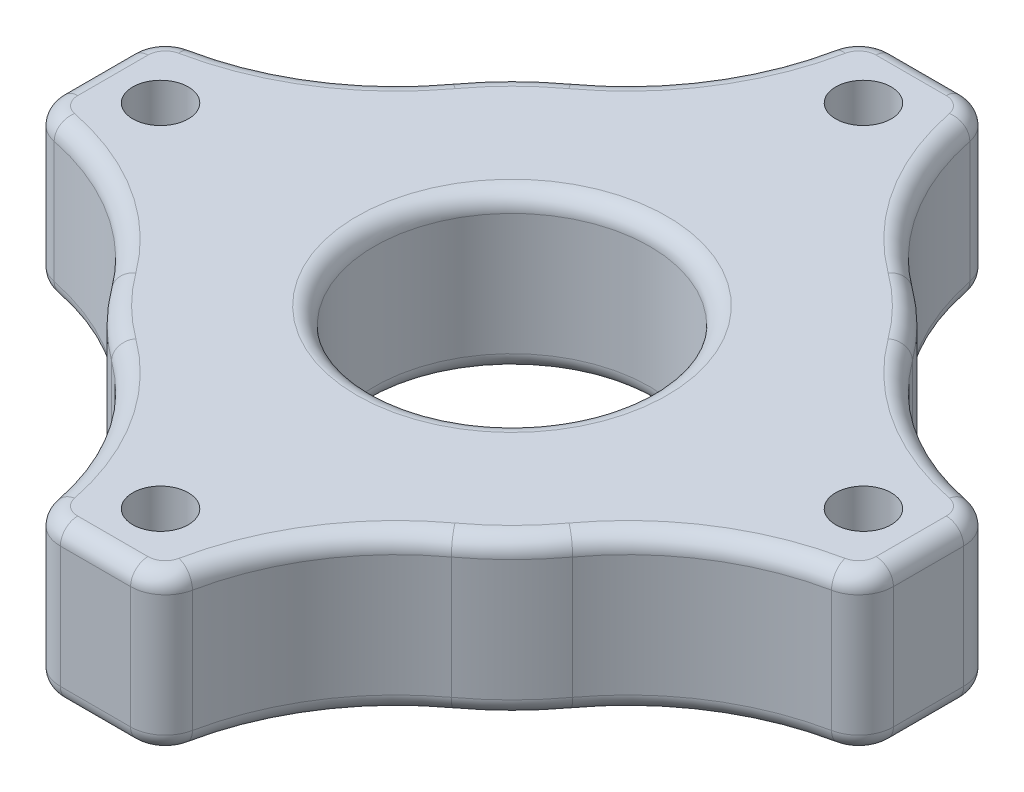
SolidWorks part; units mm, degrees
ref_plane "Front Plane" through (0, 0, 0) normal (0, 0, 1) x (1, 0, 0)
ref_plane "Top Plane" through (0, 0, 0) normal (0, 1, 0) x (1, 0, 0)
ref_plane "Right Plane" through (0, 0, 0) normal (1, 0, 0) x (0, 0, -1)
sketch "Geometry" plane through (0, 0, 0) normal (0, 1, 0) x (1, 0, 0)
  line L2 (-55, 0) -> (55, 0) construction
  line L3 (-24, -3.75) -> (24, -3.75) construction
  line L4 (-24, -3.75) -> (-24, 3.75) construction
  line L5 (-24, 3.75) -> (24, 3.75) construction
  line L6 (24, -3.75) -> (24, 3.75) construction
  line L7 (-24, -3.75) -> (24, 3.75) construction
  line L8 (-24, 3.75) -> (24, -3.75) construction
  line L9 (-3.75, -24) -> (3.75, -24) construction
  line L10 (-3.75, -24) -> (-3.75, 24) construction
  line L11 (-3.75, 24) -> (3.75, 24) construction
  line L12 (3.75, -24) -> (3.75, 24) construction
  line L13 (-3.75, -24) -> (3.75, 24) construction
  line L14 (-3.75, 24) -> (3.75, -24) construction
  line L15 (-16.0682, 3.75) -> (-24, 3.75)
  line L16 (-24, 3.75) -> (-24, -3.75)
  line L17 (-24, -3.75) -> (-16.0682, -3.75)
  line L18 (3.75, 16.0682) -> (3.75, 24)
  line L19 (3.75, 24) -> (-3.75, 24)
  line L20 (-3.75, 24) -> (-3.75, 16.0682)
  line L21 (16.0682, -3.75) -> (24, -3.75)
  line L22 (24, -3.75) -> (24, 3.75)
  line L23 (24, 3.75) -> (16.0682, 3.75)
  line L24 (-3.75, -16.0682) -> (-3.75, -24)
  line L25 (-3.75, -24) -> (3.75, -24)
  line L26 (3.75, -24) -> (3.75, -16.0682)
  circle A0 centre (0, 0) radius 7.9375
  circle A1 centre (0, 0) radius 16.5
  circle A2 centre (-20.25, 0) radius 1.6
  circle A3 centre (0, 20.25) radius 1.6
  circle A4 centre (20.25, 0) radius 1.6
  circle A5 centre (0, -20.25) radius 1.6
  circle A6 centre (-20.25, 0) radius 2.75
  circle A7 centre (0, 20.25) radius 2.75
  circle A8 centre (20.25, 0) radius 2.75
  circle A9 centre (0, -20.25) radius 2.75
  dimension "D1" = 15.875
  dimension "D2" = 33
  dimension "D6" = 3.2
  dimension "D8" = 5.5
  dimension "D3" = 7.5
  dimension "D4" = 24
  dimension "D5" = 3.75
  dimension "D7" = 4
  dimension "D9" = 4
  dimension "D10" = 4
extrude "Cap and Holes" add sketch "Geometry" along normal blind 9 contours A1 A0 | A1 L15 L16 L17 A6 | A1 L24 L25 L26 A9 | A1 L21 L22 L23 A8 | A1 L18 L19 L20 A7 | A7 A3 | A6 A2 | A9 A5 | A8 A4 region at (-16.6092, 0, 0) region at (-11.3373, 0, -11.3373) region at (-3.6408, 0, -20.0341) region at (0, 0, 16.6092) region at (20.0341, 0, -3.6408) region at (-22.9222, 0, 0) region at (-2.6722, 0, -20.25) region at (17.5778, 0, 0) region at (-2.6722, 0, 20.25)
extrude "Socket_Head" cut sketch "Sketch1<3>" along normal blind 3 contours A9 A5 | A8 A4 | A7 A3 | A6 A2 region at (-22.9222, 0, 0) region at (-2.6722, 0, -20.25) region at (17.5778, 0, 0) region at (-2.6722, 0, 20.25)
sketch "Sketch1<3>" plane through (0, 0, 0) normal (0, 1, 0) x (1, 0, 0) same geometry as "Geometry"
fillet "Fillet1" radius 15 8 edges at (-16.0682, 4.5, 3.75) (-3.75, 4.5, 16.0682) (-3.75, 4.5, -16.0682) (-16.0682, 4.5, -3.75) (3.75, 4.5, -16.0682) (16.0682, 4.5, -3.75) (16.0682, 4.5, 3.75) (3.75, 4.5, 16.0682)
fillet "Fillet2" radius 2 8 edges at (-3.75, 4.5, -24) (3.75, 4.5, -24) (24, 4.5, -3.75) (24, 4.5, 3.75) (3.75, 4.5, 24) (-3.75, 4.5, 24) (-24, 4.5, 3.75) (-24, 4.5, -3.75)
fillet "Fillet3" radius 1 50 edges at (-11.6673, 0, -11.6673) (-17.2978, 0, -6.0376) (-23.5476, 0, -3.2902) (-24, 0, 0) (-23.5476, 0, 3.2902) (-17.2978, 0, 6.0376) (-11.6673, 0, 11.6673) (-6.0376, 0, 17.2978) (-3.2902, 0, 23.5476) (0, 0, 24) (3.2902, 0, 23.5476) (6.0376, 0, 17.2978) (11.6673, 0, 11.6673) (17.2978, 0, 6.0376) (23.5476, 0, 3.2902) (24, 0, 0) (23.5476, 0, -3.2902) (17.2978, 0, -6.0376) (11.6673, 0, -11.6673) (6.0376, 0, -17.2978) (3.2902, 0, -23.5476) (0, 0, -24) (-3.2902, 0, -23.5476) (11.6673, 9, 11.6673) (6.0376, 9, 17.2978) (3.2902, 9, 23.5476) (0, 9, 24) (-3.2902, 9, 23.5476) (-6.0376, 9, 17.2978) (-11.6673, 9, 11.6673) (-17.2978, 9, 6.0376) (-23.5476, 9, 3.2902) (-24, 9, 0) (-23.5476, 9, -3.2902) (-17.2978, 9, -6.0376) (-11.6673, 9, -11.6673) (-6.0376, 9, -17.2978) (-3.2902, 9, -23.5476) (0, 9, -24) (3.2902, 9, -23.5476) (6.0376, 9, -17.2978) (11.6673, 9, -11.6673) (17.2978, 9, -6.0376) (23.5476, 9, -3.2902) (24, 9, 0) (23.5476, 9, 3.2902) (-6.0376, 0, -17.2978) (17.2978, 9, 6.0376) (0, 9, 7.9375) (0, 0, 7.9375)
